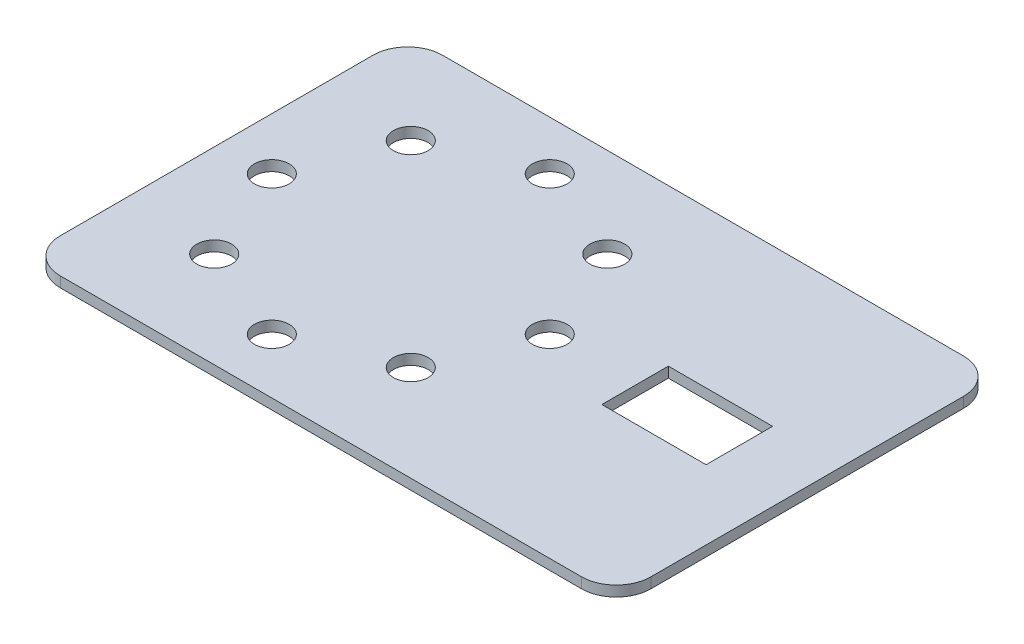
SolidWorks part; units mm, degrees
ref_plane "Front Plane" through (0, 0, 0) normal (0, 0, 1) x (1, 0, 0)
ref_plane "Top Plane" through (0, 0, 0) normal (0, 1, 0) x (1, 0, 0)
ref_plane "Right Plane" through (0, 0, 0) normal (1, 0, 0) x (0, 0, -1)
sketch "Sketch1" plane through (0, 0, 0) normal (0, 1, 0) x (1, 0, 0)
  line L0 (-37.5, 0) -> (-15, 0) construction
  line L6 (42.5, -27.9333) -> (-42.5, -27.9333)
  line L7 (32.5, -5) -> (17.5, -5)
  line L8 (32.5, -5) -> (32.5, 4.5667)
  line L9 (32.5, 4.5667) -> (17.5, 4.5667)
  line L10 (17.5, -5) -> (17.5, 4.5667)
  line L11 (32.5, -5) -> (17.5, 4.5667) construction
  line L12 (32.5, 4.5667) -> (17.5, -5) construction
  line L13 (42.5, -27.9333) -> (42.5, 27.0667)
  line L14 (42.5, 27.0667) -> (-42.5, 27.0667)
  line L15 (-42.5, -27.9333) -> (-42.5, 27.0667)
  circle A0 centre (-35, 0) radius 2.5
  circle A2 centre (-29.1421, 14.1421) radius 2.5
  circle A3 centre (-15, 20) radius 2.5
  circle A4 centre (-0.8579, 14.1421) radius 2.5
  circle A5 centre (5, 0) radius 2.5
  circle A6 centre (-0.8579, -14.1421) radius 2.5
  circle A7 centre (-15, -20) radius 2.5
  circle A8 centre (-29.1421, -14.1421) radius 2.5
  point P0 (0, 0)
  point P6 (25, -0.2166)
  dimension "D3" = 5
  dimension "D4" = 10
  dimension "D1" = 55
  dimension "D2" = 85
  dimension "D5" = 22.5
  dimension "D6" = 22.5
  dimension "D9" = 15
  dimension "D7" = 8
extrude "Boss-Extrude3" add sketch "Sketch1" along normal blind 1.5
fillet "Fillet2" radius 5 4 edges at (42.5, 0.75, -27.0667) (-42.5, 0.75, -27.0667) (-42.5, 0.75, 27.9333) (42.5, 0.75, 27.9333)
